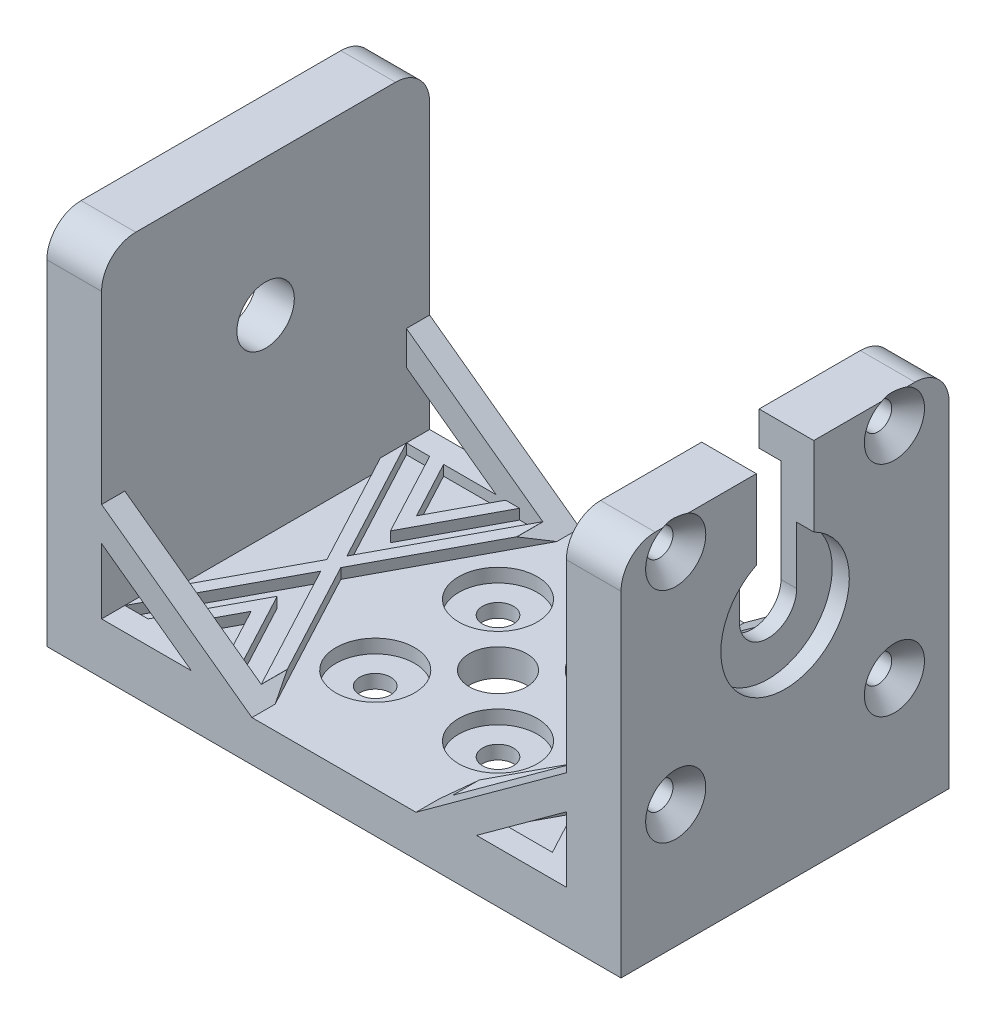
SolidWorks part; units mm, degrees
material "Custom Plastic"
ref_plane "Front Plane" through (0, 0, 0) normal (0, 0, 1) x (1, 0, 0)
ref_plane "Top Plane" through (0, 0, 0) normal (0, 1, 0) x (1, 0, 0)
ref_plane "Right Plane" through (0, 0, 0) normal (1, 0, 0) x (0, 0, -1)
sketch "Sketch1" plane through (0, 0, 0) normal (0, 1, 0) x (1, 0, 0)
  line L1 (21, -12) -> (-21, -12)
  line L2 (21, -12) -> (21, 12)
  line L3 (21, 12) -> (-21, 12)
  line L4 (-21, -12) -> (-21, 12)
  line L5 (21, -12) -> (-21, 12) construction
  line L6 (21, 12) -> (-21, -12) construction
  point P0 (0, 0)
  dimension "D1" = 42
  dimension "D2" = 24
extrude "Boss-Extrude1" add sketch "Sketch1" along normal blind 3
sketch "Sketch2" plane through (0, 3, 0) normal (0, 1, 0) x (1, 0, 0)
  line L0 (21, -12) -> (21, 12) construction
  line L1 (-21, 12) -> (-21, -12) construction
  line L2 (21, -12) -> (21, 12)
  line L3 (-21, 12) -> (-21, -12)
  line L4 (-17, 12) -> (-17, -12)
  line L5 (17, -12) -> (17, 12)
  line L6 (17, 12) -> (21, 12)
  line L7 (17, -12) -> (21, -12)
  line L8 (-17, -12) -> (-21, -12)
  line L9 (-17, 12) -> (-21, 12)
  dimension "D2" = 4
extrude "Boss-Extrude2" add sketch "Sketch2" along normal blind 24
sketch "Sketch3" plane through (21, 0, 0) normal (1, 0, 0) x (0, 0, -1)
  line L0 (-12, 27) -> (12, 27) construction
  circle A4 centre (0, 17) radius 2.1
  dimension "D1" = 4.2
  dimension "D2" = 10
extrude "Cut-Extrude1" cut sketch "Sketch3" against normal through all
sketch "Sketch4" plane through (17, 0, 0) normal (-1, 0, 0) x (0, 0, 1)
  circle A0 centre (0, 17) radius 7.8
  dimension "D1" = 15.6
extrude "Cut-Extrude2" cut sketch "Sketch4" against normal blind 1.6
sketch "Sketch5" plane through (21, 0, 0) normal (1, 0, 0) x (0, 0, -1)
  line L0 (-12, 27) -> (-12, 0) construction
  line L1 (-12, 27) -> (12, 27) construction
  circle A8 centre (-8, 25) radius 1
  circle A9 centre (8, 25) radius 1
  circle A10 centre (8, 9) radius 1
  circle A11 centre (-8, 9) radius 1
  dimension "D1" = 2
  dimension "D2" = 2
  dimension "D3" = 2
  dimension "D4" = 2
  dimension "D5" = 16
  dimension "D6" = 16
  dimension "D7" = 16
  dimension "D8" = 16
  dimension "D9" = 4
  dimension "D10" = 2
extrude "Cut-Extrude3" cut sketch "Sketch5" against normal up to next
chamfer "Chamfer1" distance 1.2 angle 45 4 edges at (21, 9, -9) (21, 9, 7) (21, 25, 7) (21, 25, -9)
fillet "Fillet1" radius 2.5 1 edges at (19, 27, 12) type face fillet first side face at (0, 14.25, 12) second side face at (19.9503, 27, 0.0171)
fillet "Fillet2" radius 2.5 1 edges at (19, 27, -12) type face fillet first side face at (0, 14.25, -12) second side face at (19.9503, 27, -0.6079)
fillet "Fillet3" radius 2.5 1 edges at (-19, 27, -12) type face fillet first side face at (0, 13.625, -12) second side face at (-19, 27, 0)
fillet "Fillet4" radius 2.5 1 edges at (-19, 27, 12) type face fillet first side face at (0, 13.625, 12) second side face at (-19, 27, 1.25)
sketch "Sketch6" plane through (0, 0, 0) normal (0, -1, 0) x (1, 0, 0)
  circle A0 centre (0, 0) radius 2.1
  dimension "D1" = 4.2
extrude "Cut-Extrude4" cut sketch "Sketch6" against normal up to next
sketch "Sketch7" plane through (21, 0, 0) normal (1, 0, 0) x (0, 0, -1)
  circle A0 centre (0, 17) radius 4.7
  dimension "D1" = 9.4
extrude "Cut-Extrude5" cut sketch "Sketch7" against normal blind 1.25
ref_plane "Plane1" through (0, 0, 0) normal (1, 0, 0) x (0, 0, -1)
mirror "Mirror1" about plane through (0, 0, 0) normal (1, 0, 0) of "Cut-Extrude5"
sketch "Sketch9" plane through (0, 0, 12) normal (0, 0, 1) x (1, 0, 0)
  line L5 (-17, 3) -> (-17, 11)
  line L6 (-17, 24.5) -> (-17, 3) construction
  line L7 (-17, 11) -> (-6, 3)
  line L8 (-17, 3) -> (17, 3) construction
  line L9 (-6, 3) -> (-17, 3)
  line L10 (0, -4.7081) -> (0, 14.9704) construction
  line L11 (17, 11) -> (6, 3)
  line L12 (17, 3) -> (17, 11)
  line L13 (6, 3) -> (17, 3)
  dimension "D1" = 11
  dimension "D2" = 8
extrude "Boss-Extrude3" add sketch "Sketch9" against normal offset from surface (1.6999 mm away) 0.3
sketch "Sketch10" plane through (21, 0, 0) normal (1, 0, 0) x (0, 0, -1)
  line L0 (2.1, 17) -> (2.1, 27)
  line L1 (-7.0835, 27) -> (7.0835, 27) construction
  line L2 (2.1, 27) -> (-2.1, 27)
  line L3 (-2.1, 17) -> (-2.1, 27)
  circle A0 centre (0, 17) radius 2.1 construction
  arc A1 (-2.1, 17) -> (2.1, 17) centre (0, 17) ccw
extrude "Cut-Extrude6" cut sketch "Sketch10" against normal up to next
ref_plane "Plane2" through (0, 0, 0) normal (0, 0, 1) x (1, 0, 0)
sketch "Sketch11" plane through (0, 0, -12) normal (0, 0, -1) x (-1, 0, 0)
  line L0 (-17, 3) -> (-17, 11)
  line L1 (-17, 8.5) -> (-17, 25.5) construction
  line L2 (-17, 11) -> (-6, 3)
  line L3 (-17, 3) -> (17, 3) construction
  line L4 (-6, 3) -> (-17, 3)
  line L5 (0, -7.0454) -> (0, 31.7819) construction
  line L6 (17, 11) -> (6, 3)
  line L7 (17, 3) -> (17, 11)
  line L8 (6, 3) -> (17, 3)
  dimension "D1" = 11
  dimension "D2" = 8
extrude "Boss-Extrude4" add sketch "Sketch11" against normal offset from surface (1.6999 mm away) 0.3
sketch "Sketch12" plane through (0, 0, 0) normal (0, -1, 0) x (1, 0, 0)
  circle A0 centre (0, 0) radius 9.6
  dimension "D1" = 19.2
extrude "Cut-Extrude7" cut sketch "Sketch12" against normal blind 1
sketch "Sketch13" plane through (0, 1, 0) normal (0, -1, 0) x (1, 0, 0)
  line L0 (0, -14.8301) -> (0, 17.0494) construction
  line L1 (-12.9207, 0) -> (13.2316, 0) construction
  circle A0 centre (-4.4902, 4.4901) radius 1.1303
  circle A1 centre (4.4901, 4.4901) radius 1.1303
  circle A2 centre (4.4901, -4.4901) radius 1.1303
  circle A3 centre (-4.4902, -4.4902) radius 1.1303
  dimension "D1" = 2.2606
  dimension "D2" = 8.9803
  dimension "D6" = 2.2606
  dimension "D7" = 2.2606
  dimension "D8" = 2.2606
  dimension "D3" = 8.9803
  dimension "D4" = 4.4901
  dimension "D5" = 4.4901
extrude "Cut-Extrude8" cut sketch "Sketch13" against normal up to next
sketch "Sketch14" plane through (0, 3, 0) normal (0, 1, 0) x (1, 0, 0)
  line L0 (-6, 10.3001) -> (-11.5, 0)
  line L1 (-6, -10.3001) -> (-11.5, 0)
  line L2 (-17, -8.3894) -> (-12.519, 0.0024)
  line L3 (-17, -9.5) -> (-17, 9.5) construction
  line L4 (-17, 10.3001) -> (-6, 10.3001) construction
  line L5 (-7.0177, -10.3001) -> (-12.0088, -0.9529)
  line L6 (-17, -10.3001) -> (-6, -10.3001) construction
  line L7 (-12.519, 0.0024) -> (-17, 8.3942)
  line L8 (-12.0088, -0.9529) -> (-17, -10.3001)
  line L9 (-9.7384, -10.3001) -> (-12.0088, -6.0482)
  line L10 (-12.0088, -6.0482) -> (-14.2793, -10.3001)
  line L11 (-12.0101, 0.9554) -> (-7.0203, 10.3001)
  line L12 (-12.0101, 0.9554) -> (-17, 10.3001)
  line L13 (-14.8829, -9.5199) -> (-12.0101, -4.1399)
  line L14 (-8.7207, 10.3001) -> (-9.741, 10.3001)
  line L15 (-8.7207, -10.3001) -> (-12.0101, -4.1399)
  line L16 (-8.7207, 10.3001) -> (-12.0088, 4.1423)
  line L17 (-12.0101, 6.0506) -> (-14.2793, 10.3001)
  line L18 (-12.0101, 6.0506) -> (-9.741, 10.3001)
  line L19 (-12.0088, 4.1423) -> (-15.297, 10.3001)
  line L20 (-9.7983, 0.0024) -> (-14.8829, 9.5247) construction
  line L21 (-14.8829, -9.5199) -> (-9.7983, 0.0024) construction
  line L22 (-8.1171, 11.4306) -> (-14.2207, 0) construction
  line L23 (-8.1171, -11.4306) -> (-14.2207, 0) construction
  line L24 (-6, 10.3001) -> (-17, 10.3001) construction
  line L25 (-14.2793, 10.3001) -> (-15.297, 10.3001)
  line L26 (-12.0101, 6.0506) -> (-9.1374, 11.4306) construction
  line L27 (-6, 10.3001) -> (-7.0203, 10.3001)
  line L28 (-12.0101, 6.0506) -> (-14.8829, 11.4306) construction
  line L29 (-17, 8.3942) -> (-17, 10.3001)
  line L30 (-6, -10.3001) -> (-7.0177, -10.3001)
  line L31 (-17, -10.3001) -> (-17, -8.3894)
  line L32 (-14.2793, -10.3001) -> (-15.297, -10.3001)
  line L33 (-6, -10.3001) -> (-17, -10.3001) construction
  line L34 (-9.7384, -10.3001) -> (-8.7207, -10.3001)
  line L35 (-14.8829, -9.5199) -> (-15.297, -10.3001)
  line L36 (-9.1348, -11.4306) -> (-12.0088, -6.0482) construction
  line L37 (-12.0088, -6.0482) -> (-14.8829, -11.4306) construction
  line L38 (0, -16.3518) -> (0, 17.3495) construction
  line L39 (14.8829, -9.5199) -> (12.0101, -4.1399)
  line L40 (8.7207, -10.3001) -> (12.0101, -4.1399)
  line L41 (9.7384, -10.3001) -> (8.7207, -10.3001)
  line L42 (9.7384, -10.3001) -> (12.0088, -6.0482)
  line L43 (12.0088, -6.0482) -> (14.2793, -10.3001)
  line L44 (14.2793, -10.3001) -> (15.297, -10.3001)
  line L45 (14.8829, -9.5199) -> (15.297, -10.3001)
  line L46 (12.0101, 6.0506) -> (9.741, 10.3001)
  line L47 (8.7207, 10.3001) -> (9.741, 10.3001)
  line L48 (8.7207, 10.3001) -> (12.0088, 4.1423)
  line L49 (12.0088, 4.1423) -> (15.297, 10.3001)
  line L50 (14.2793, 10.3001) -> (15.297, 10.3001)
  line L51 (12.0101, 6.0506) -> (14.2793, 10.3001)
  line L52 (12.0088, -0.9529) -> (17, -10.3001)
  line L53 (7.0177, -10.3001) -> (12.0088, -0.9529)
  line L54 (6, -10.3001) -> (7.0177, -10.3001)
  line L55 (6, -10.3001) -> (11.5, 0)
  line L56 (6, 10.3001) -> (11.5, 0)
  line L57 (6, 10.3001) -> (7.0203, 10.3001)
  line L58 (12.0101, 0.9554) -> (7.0203, 10.3001)
  line L59 (12.0101, 0.9554) -> (17, 10.3001)
  line L60 (17, 8.3942) -> (17, 10.3001)
  line L61 (12.519, 0.0024) -> (17, 8.3942)
  line L62 (17, -8.3894) -> (12.519, 0.0024)
  line L63 (17, -10.3001) -> (17, -8.3894)
  dimension "D1" = 0.8977
  dimension "D2" = 0.9
  dimension "D3" = 2.4
  dimension "D4" = 2.4
  dimension "D5" = 2.4
  dimension "D6" = 2.4
extrude "Boss-Extrude5" add sketch "Sketch14" along normal blind 0.75
sketch "Sketch16" plane through (0, 0, 10.3001) normal (0, 0, 1) x (1, 0, 0)
  line L4 (-7.0177, 3.7401) -> (-6, 3)
  line L5 (-6, 3) -> (-6, 3.75)
  line L6 (-6, 3.75) -> (-7.0177, 3.75)
  line L7 (-7.0177, 3.75) -> (-7.0177, 3.7401)
  line L8 (-7.0177, 3.7401) -> (-6, 3)
  line L9 (-6, 3) -> (-6, 3.75)
  line L10 (-6, 3.75) -> (-7.0177, 3.75)
  line L11 (-7.0177, 3.75) -> (-7.0177, 3.7401)
  dimension "D1" = 0
extrude "Cut-Extrude9" cut sketch "Sketch16" against normal through all
sketch "Sketch17" plane through (0, 0, 10.3001) normal (0, 0, 1) x (1, 0, 0)
  line L4 (6, 3) -> (7.0177, 3.7401)
  line L5 (7.0177, 3.7401) -> (7.0177, 3.75)
  line L6 (7.0177, 3.75) -> (6, 3.75)
  line L7 (6, 3.75) -> (6, 3)
  line L8 (6, 3) -> (7.0177, 3.7401)
  line L9 (7.0177, 3.7401) -> (7.0177, 3.75)
  line L10 (7.0177, 3.75) -> (6, 3.75)
  line L11 (6, 3.75) -> (6, 3)
  dimension "D1" = 0
extrude "Cut-Extrude10" cut sketch "Sketch17" against normal through all
sketch "Sketch18" plane through (0, 0, -12) normal (0, 0, -1) x (-1, 0, 0)
  line L1 (-6, 3) -> (-17, 11) construction
  line L2 (0, -14.4381) -> (0, 17.4723) construction
  line L3 (15.297, 3.75) -> (17, 3.75)
  line L4 (-10.4316, 3.75) -> (-17, 8.527)
  line L5 (17, 8.527) -> (17, 3.75)
  line L6 (-15.297, 3.75) -> (-14.2793, 3.75) construction
  line L7 (-15.297, 3.75) -> (-14.2793, 3.75)
  line L8 (-14.2793, 3.75) -> (-10.4316, 3.75)
  line L9 (-15.297, 3.75) -> (-17, 3.75)
  line L11 (-17, 8.527) -> (-17, 3.75)
  line L12 (10.4316, 3.75) -> (17, 8.527)
  line L13 (14.2793, 3.75) -> (10.4316, 3.75)
  line L14 (15.297, 3.75) -> (14.2793, 3.75)
  point P4 (-7.1763, 2.3825)
  point P5 (-18.1763, 10.3825)
  dimension "D1" = 2
extrude "Cut-Extrude11" cut sketch "Sketch18" against normal through all
sketch "Sketch19" plane through (0, 3, 0) normal (0, 1, 0) x (1, 0, 0)
  circle A0 centre (-4.4902, -4.4901) radius 2.875
  circle A1 centre (4.4901, -4.4901) radius 2.875
  circle A2 centre (-4.4902, 4.4902) radius 2.875
  circle A3 centre (4.4901, 4.4901) radius 2.875
  dimension "D1" = 5.75
  dimension "D2" = 5.75
  dimension "D3" = 5.75
  dimension "D4" = 5.75
extrude "Cut-Extrude12" cut sketch "Sketch19" against normal blind 1
equation "\"W\"= 24"
equation "\"L\"= 44"
equation "\"WT\"= 4"
equation "\"BT\"= 3"
equation "\"H\"= 24"
equation "\"BW\"=4"
equation "\"D1@Boss-Extrude1\"=\"BT\""
equation "\"D1@Sketch2\"=\"WT\""
equation "\"D2@Sketch2\"=\"WT\""
equation "\"D1@Boss-Extrude2\"=\"H\""
equation "\"SH\"= 4.2"
equation "\"D1@Sketch6\"=\"SH\""
equation "\"M2\"= 2"
equation "\"D1@Sketch5\"=\"M2\""
equation "\"D2@Sketch5\"=\"M2\""
equation "\"D3@Sketch5\"=\"M2\""
equation "\"D4@Sketch5\"=\"M2\""
equation "\"D1@Sketch9\"=\"L\"*(1/4)"
equation "\"D2@Sketch9\"=\"H\"*(1/3)"
equation "\"D1@Sketch11\"=\"L\"*0.25"
equation "\"D2@Sketch11\"=\"H\"*(1/3)"
